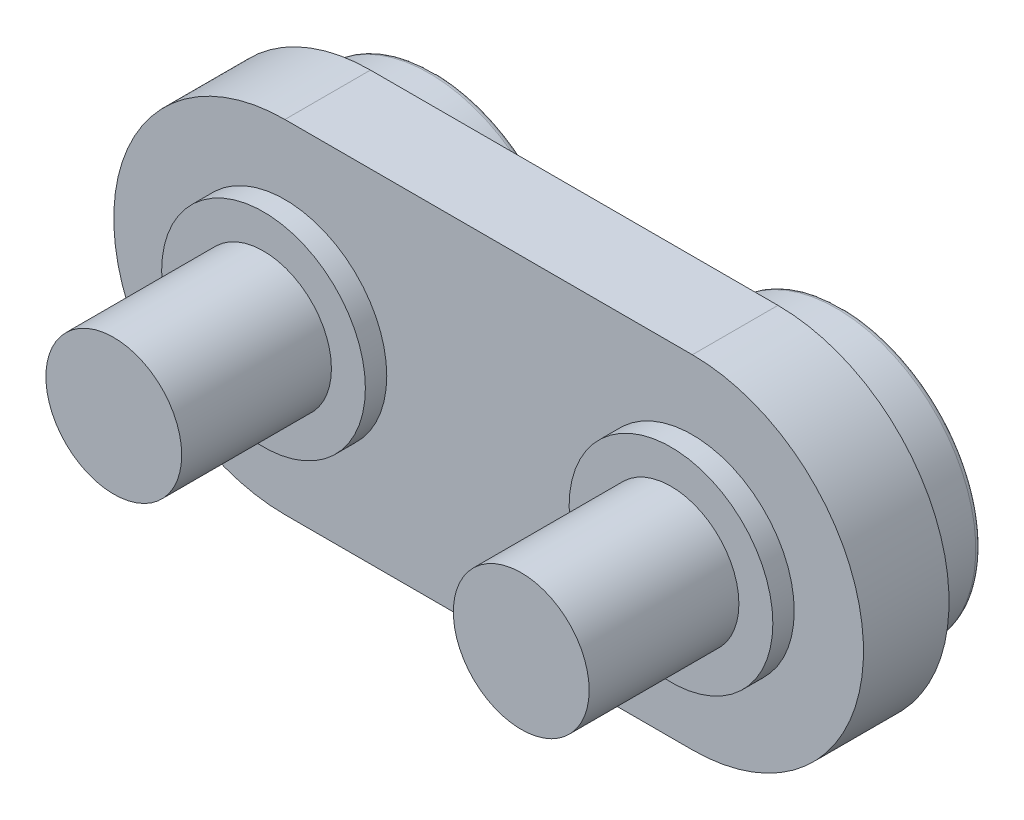
SolidWorks part; units mm, degrees
material "PBT General Purpose"
ref_plane "Top Plane" through (0, 0, 0) normal (0, 0, 1) x (1, 0, 0)
ref_plane "Right Plane" through (0, 0, 0) normal (0, 1, 0) x (1, 0, 0)
ref_plane "Front Plane" through (0, 0, 0) normal (1, 0, 0) x (0, 0, -1)
sketch "Sketch1" plane through (0, 0, 0) normal (0, 0, 1) x (1, 0, 0)
  line L1 (-9.525, 8) -> (9.525, 8)
  line L3 (-9.525, -8) -> (9.525, -8)
  line L5 (-9.525, 8) -> (9.525, -8) construction
  line L6 (-9.525, -8) -> (9.525, 8) construction
  arc A0 (-9.525, 8) -> (-9.525, -8) centre (-9.525, 0) ccw
  arc A1 (9.525, 8) -> (9.525, -8) centre (9.525, 0) cw
  circle A2 centre (-9.525, 0) radius 2.11
  circle A3 centre (9.525, 0) radius 2.11
  point P0 (0, 0)
  dimension "D2" = 19.05
  dimension "D3" = 4.22
  dimension "D1" = 16
extrude "Boss-Extrude1" add sketch "Sketch1" along normal blind 4
sketch "Sketch2" plane through (0, 0, 0) normal (0, 0, -1) x (-1, 0, 0)
  circle A0 centre (-9.525, 0) radius 6.5
  circle A1 centre (9.525, 0) radius 6.5
  circle A2 centre (-9.525, 0) radius 2.11
  circle A3 centre (9.525, 0) radius 2.11
  circle A4 centre (-9.525, 0) radius 2.11 construction
  dimension "D1" = 13
extrude "Boss-Extrude2" add sketch "Sketch2" along normal blind 3 separate body
fillet "Fillet1" radius 0.25 1 edges at (-16.025, 0, -3)
chamfer "Chamfer1" distance 1 angle 30 1 edges at (-11.635, 0, -3) first distance on face at (-15.775, 0, -3)
sketch "Sketch3" plane through (0, 0, 4) normal (0, 0, 1) x (1, 0, 0)
  circle A0 centre (-9.525, 0) radius 4.7625
  circle A1 centre (9.525, 0) radius 4.7625
  circle A2 centre (-9.525, 0) radius 2.11 construction
  circle A3 centre (9.525, 0) radius 2.11 construction
  circle A4 centre (-9.525, 0) radius 2.11
  circle A5 centre (9.525, 0) radius 2.11
  dimension "D1" = 9.525
extrude "Boss-Extrude3" add sketch "Sketch3" along normal blind 1 separate body
sketch "Sketch4" plane through (0, 0, 5) normal (0, 0, 1) x (1, 0, 0)
  circle A0 centre (-9.525, 0) radius 3.175
  circle A1 centre (9.525, 0) radius 3.175
  dimension "D1" = 6.35
extrude "Boss-Extrude4" add sketch "Sketch4" along normal blind 7 separate body
fillet "Fillet2" radius 0.25 1 edges at (3.025, 0, -3)
chamfer "Chamfer2" distance 1 angle 30 1 edges at (7.415, 0, -3) first distance on face at (3.275, 0, -3)
ref_axis "Axis1" through (-9.525, 0, 12) along (0, 0, -1)
ref_axis "Axis2" through (9.525, 0, 12) along (0, 0, -1)
